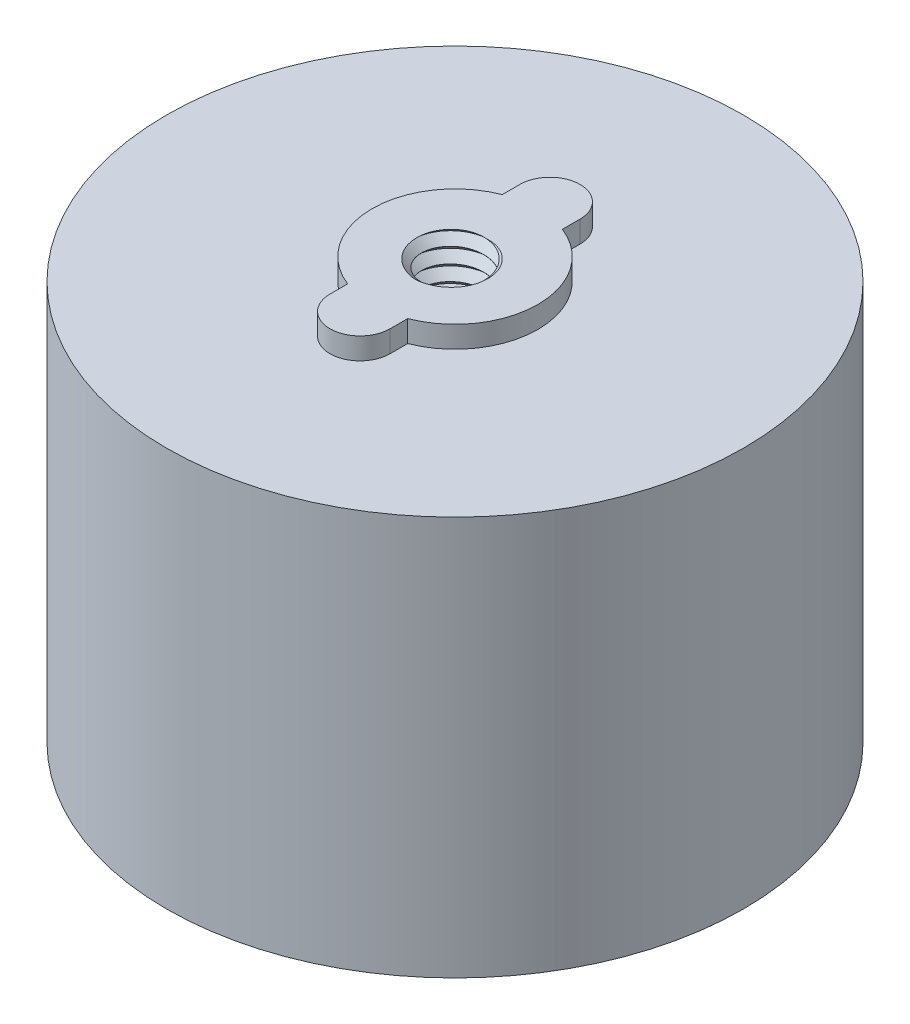
SolidWorks part; units mm, degrees
note: The reader was unsure of these and kept them because the rebuilt part matched: shared geometry of "草图1<2>", "草图3<2>".
ref_plane "前视基准面" through (0, 0, 0) normal (0, 0, 1) x (1, 0, 0)
ref_plane "上视基准面" through (0, 0, 0) normal (0, 1, 0) x (1, 0, 0)
ref_plane "右视基准面" through (0, 0, 0) normal (1, 0, 0) x (0, 0, -1)
sketch "草图1" plane through (0, 0, 0) normal (0, 1, 0) x (1, 0, 0)
  line L0 (0, -16) -> (0, 0) construction
  circle A0 centre (0, 16) radius 1.7
  circle A2 centre (0, -16) radius 1.7
  circle A4 centre (0, 0) radius 24
  point P5 (0, 0)
  dimension "D2" = 2
  dimension "D3" = 3.4
  dimension "D4" = 48
  dimension "D1" = 16
extrude "凸台-拉伸1" add sketch "草图1" against normal blind 25
extrude "凸台-拉伸2" add sketch "草图1<2>" along normal blind 10
sketch "草图1<2>" plane through (0, 0, 0) normal (0, 1, 0) x (1, 0, 0) same geometry as "草图1"
sketch "草图2" plane through (0, 10, 0) normal (0, 1, 0) x (1, 0, 0)
  line L0 (0, 7.9) -> (0, -7.9) construction
  line L1 (2.5, 7.9) -> (2.5, -7.9)
  line L2 (-2.5, 7.9) -> (-2.5, -7.9)
  circle A0 centre (0, 0) radius 6.9
  arc A1 (2.5, 7.9) -> (-2.5, 7.9) centre (0, 7.9) ccw
  arc A2 (-2.5, -7.9) -> (2.5, -7.9) centre (0, -7.9) ccw
  circle A3 centre (0, 0) radius 24
  circle A4 centre (0, 0) radius 24 construction
  point P4 (0, 0)
  circle M3 centre (0, 0) radius 24
  dimension "D1" = 13.8
  dimension "D3" = 2.5
  dimension "D2" = 15.8
extrude "切除-拉伸1" cut sketch "草图2" against normal blind 1.8 contours A2 L2 A0 A1 L1 M3
sketch "草图3" plane through (0, 10, 0) normal (0, 1, 0) x (1, 0, 0)
  circle A0 centre (0, 0) radius 2.6
  dimension "D1" = 5.2
curve "螺旋线/涡状线1" pitch 1.27 height 15.24 turns 12
extrude "切除-拉伸2" cut sketch "草图3<2>" against normal blind 15
sketch "草图3<2>" plane through (0, 10, 0) normal (0, 1, 0) x (1, 0, 0) same geometry as "草图3"
sketch "草图4" plane through (0, 0, 0) normal (1, 0, 0) x (0, 0, -1)
  line L0 (-2.6, 10) -> (-2.6, 9.37)
  line L1 (-2.6, 9.37) -> (-3.3, 10)
  line L2 (6.4312, 10) -> (-6.4312, 10) construction
  line L3 (-3.3, 10) -> (-2.6, 10.63)
  line L4 (-2.6, 10.63) -> (-2.6, 10)
  dimension "D1" = 0.7
  dimension "D2" = 0.63
sweep "切除-扫描1" cut profiles "草图4" path "螺旋线/涡状线1"
sketch "草图5" plane through (0, -25, 0) normal (0, -1, 0) x (1, 0, 0)
  circle A0 centre (0, 16) radius 1.7
  circle A1 centre (0, 16) radius 1.7 construction
curve "螺旋线/涡状线2" pitch 0.7 height 25.025 turns 35.75
sketch "草图7" plane through (0, 0, 0) normal (1, 0, 0) x (0, 0, -1)
  line L0 (-14.3, -25) -> (-14.3, -24.651)
  line L1 (-14.3, -24.651) -> (-14, -25)
  line L2 (-24, -25) -> (24, -25) construction
  line L3 (-14, -25) -> (-14.3, -25.349)
  line L4 (-14.3, -25.349) -> (-14.3, -25)
  dimension "D1" = 0.349
  dimension "D2" = 0.3
sweep "切除-扫描2" cut profiles "草图7" path "螺旋线/涡状线2"
pattern_circular "阵列(圆周)2" count 2 over 360 about axis through (0, -25, 0) along (0, 1, 0) of "切除-扫描2"
sketch "草图8" plane through (0, -25, 0) normal (0, -1, 0) x (1, 0, 0)
  circle A0 centre (0, 0) radius 5.1
  dimension "D1" = 10.2
extrude "切除-拉伸3" cut sketch "草图8" against normal blind 10
fillet "圆角1" radius 5 1 edges at (0, -15, -5.1)
